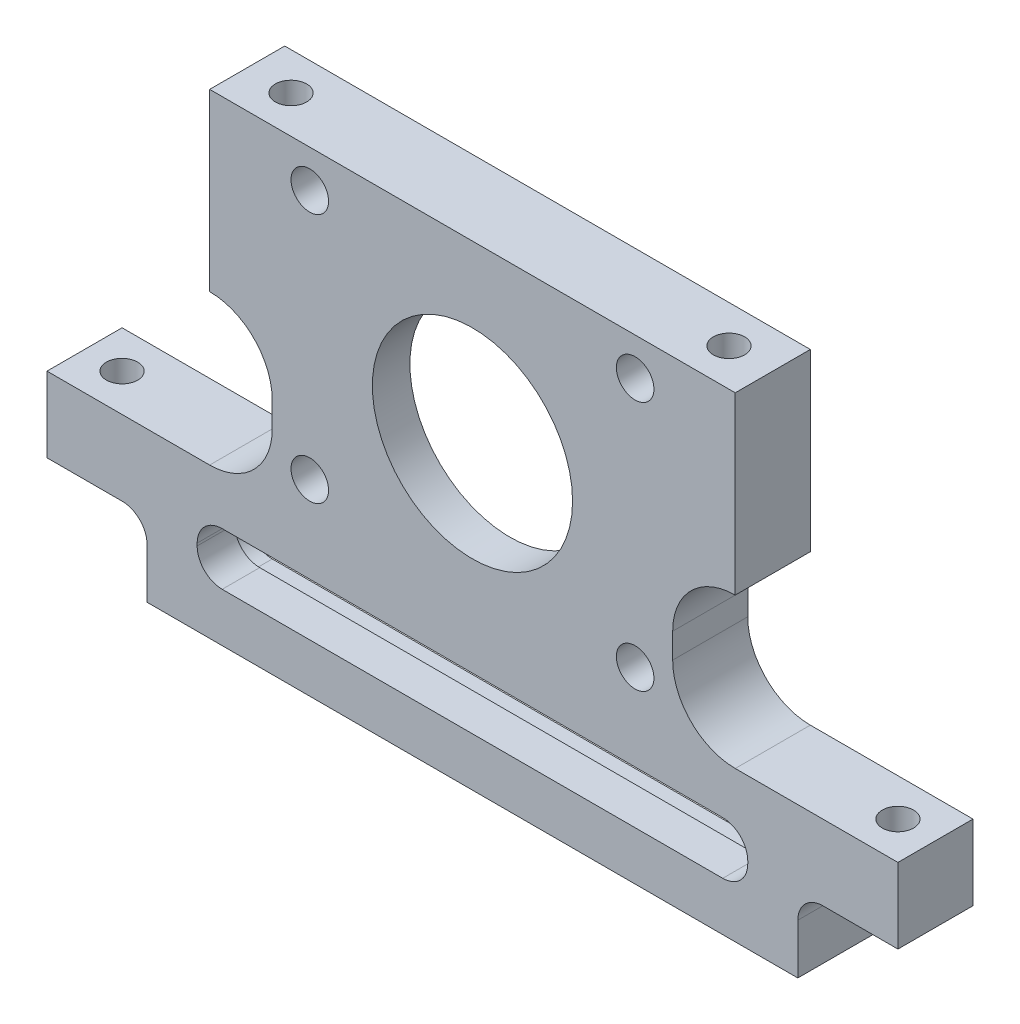
SolidWorks part; units mm, degrees
material "1060 Alloy"
ref_plane "Front Plane" through (0, 0, 0) normal (0, 0, 1) x (1, 0, 0)
ref_plane "Top Plane" through (0, 0, 0) normal (0, 1, 0) x (1, 0, 0)
ref_plane "Right Plane" through (0, 0, 0) normal (1, 0, 0) x (0, 0, -1)
sketch "Sketch1" plane through (0, 0, 0) normal (0, 0, 1) x (1, 0, 0)
  line L0 (18, 32) -> (50, 32)
  line L1 (8, 0) -> (8, -6)
  line L2 (50, 32) -> (50, 6)
  line L3 (18, 32) -> (18, 6)
  line L4 (12, 2.1) -> (56, 2.1)
  line L5 (12, 2.1) -> (12, -2.1)
  line L6 (12, -2.1) -> (56, -2.1)
  line L7 (56, 2.1) -> (56, -2.1)
  line L8 (8, -6) -> (60, -6)
  line L9 (60, -6) -> (60, 0)
  line L10 (8, 0) -> (0, 0)
  line L11 (0, 0) -> (0, 6)
  line L12 (0, 6) -> (18, 6)
  line L13 (50, 6) -> (68, 6)
  line L14 (68, 6) -> (68, 0)
  line L15 (68, 0) -> (60, 0)
  circle A0 centre (34, 18) radius 8
  dimension "D4" = 16
  dimension "D1" = 4.2
  dimension "D2" = 44
  dimension "D3" = 3.9
  dimension "D5" = 4
  dimension "D6" = 4
  dimension "D7" = 32
  dimension "D8" = 16
  dimension "D9" = 18
  dimension "D10" = 6
  dimension "D12" = 8
  dimension "D13" = 3.9
  dimension "D14" = 32
extrude "Boss-Extrude1" add sketch "Sketch1" along normal blind 6
sketch "Sketch3" plane through (0, 0, 0) normal (0, 0, -1) x (-1, 0, 0)
  circle A0 centre (-34, 18) radius 13
  dimension "D1" = 26
extrude "Cut-Extrude2" cut sketch "Sketch3" against normal offset from surface (3 mm away) 3 up to face at (34, 0, 6)
hole_wizard "Tap Drill for M3 Tap2" positions "Sketch5" profile "Sketch4" hole size "M3" standard "ISO"
sketch "Sketch5" plane through (38.1016, 0, -22.7468) normal (0, -1, 0) x (-1, 0, 0)
  line L3 (-29.8984, -28.7468) -> (-29.8984, -22.7468) construction
  line L4 (38.1016, -28.7468) -> (38.1016, -22.7468) construction
  line L5 (-21.8984, -28.7468) -> (-29.8984, -28.7468) construction
  point P0 (35.1016, -25.7468)
  point P2 (-26.8984, -25.7468)
  dimension "D1" = 3
  dimension "D2" = 3
  dimension "D3" = 3
sketch "Sketch4" plane through (3, 0, 3) normal (1, 0, 0) x (0, 0, -1)
  line L0 (0, 0) -> (0, 8.7511)
  line L1 (0, 8.7511) -> (1.25, 8)
  line L2 (1.25, 8) -> (1.25, 0)
  line L5 (1.25, 0) -> (0, 0)
  line L10 (0, 8.7511) -> (-1.25, 8) construction
  line L11 (0, -6.35) -> (0, 107.95) construction
  dimension "Hole Dia." = 2.5
  dimension "Hole Depth" = 8
  dimension "Drill Angle" = 118
sketch "Sketch10" plane through (0, 0, 0) normal (0, 0, -1) x (-1, 0, 0)
  line L0 (-56, -2.1) -> (-56, 2.1) construction
  line L1 (-58, 4) -> (-10, 4)
  line L2 (-58, 4) -> (-58, -4)
  line L3 (-58, -4) -> (-10, -4)
  line L4 (-10, 4) -> (-10, -4)
  line L8 (-56, 2.1) -> (-12, 2.1) construction
  line L9 (-12, 2.1) -> (-12, -2.1) construction
  dimension "D1" = 8
  dimension "D2" = 1.9
  dimension "D3" = 2
  dimension "D4" = 2
extrude "Cut-Extrude5" cut sketch "Sketch10" against normal blind 3
sketch "Sketch11" plane through (0, 0, 6) normal (0, 0, 1) x (1, 0, 0)
  line L1 (18, 32) -> (13, 32)
  line L2 (18, 32) -> (18, 18)
  line L3 (18, 18) -> (13, 18)
  line L4 (13, 32) -> (13, 18)
  line L6 (50, 32) -> (55, 32)
  line L7 (50, 32) -> (50, 18)
  line L8 (50, 18) -> (55, 18)
  line L9 (55, 32) -> (55, 18)
  line L10 (18, 6) -> (0, 6) construction
  dimension "D1" = 42
  dimension "D2" = 12
extrude "Boss-Extrude2" add sketch "Sketch11" against normal up to surface (6 mm away) up to face at (34, 0, 0)
fillet "Fillet1" radius 2 8 edges at (10, -4, 1.5) (12, -2.1, 4.5) (10, 4, 1.5) (12, 2.1, 4.5) (58, -4, 1.5) (58, 4, 1.5) (56, -2.1, 4.5) (56, 2.1, 4.5)
hole_wizard "M3x0.5 Tapped Hole1" positions "3DSketch1" profile "Sketch13" tap size "M3x0.5" standard "ANSI Metric"
sketch3d "3DSketch1"
  line L1 (13, 32, 0) -> (55, 32, 0) construction
  line L2 (13, 32, 0) -> (55, 32, 0) construction
  point P0 (51.5, 32, 3)
  point P2 (16.5, 32, 3)
  dimension "D1" = 35
  dimension "D2" = 3
  dimension "D3" = 3
  dimension "D4" = 1.5
sketch "Sketch13" plane through (51.5, 32, 3) normal (1, 0, 0) x (0, 0, 1)
  line L0 (0, 0) -> (0, 10.2511)
  line L1 (0, 10.2511) -> (1.25, 9.5)
  line L2 (1.25, 9.5) -> (1.25, 0)
  line L5 (1.25, 0) -> (0, 0)
  line L10 (0, 10.2511) -> (-1.25, 9.5) construction
  line L11 (0, -6.35) -> (0, 107.95) construction
  dimension "Tap Drill Dia." = 2.5
  dimension "Tap Drill Depth" = 9.5
  dimension "Drill Angle" = 118
cosmetic thread "Hole Thread1" parameters "D1"=8, "D2"=3
cosmetic thread "Hole Thread2" parameters "D1"=8, "D2"=3
fillet "Fillet3" radius 5 4 edges at (18, 18, 3) (18, 6, 3) (50, 6, 3) (50, 18, 3)
sketch "Sketch14" plane through (0, 0, 6) normal (0, 0, 1) x (1, 0, 0)
  line L0 (55, 32) -> (13, 32) construction
  line L1 (18, 32) -> (50, 32) construction
  line L2 (18, 32) -> (18, 6) construction
  line L3 (18, 6) -> (50, 6) construction
  line L4 (50, 32) -> (50, 6) construction
  line L5 (50, 11) -> (50, 13) construction
  line L6 (18, 13) -> (18, 11) construction
  line L7 (13, 6) -> (0, 6) construction
  circle A0 centre (21, 29) radius 1.5
  circle A1 centre (47, 29) radius 1.5
  circle A2 centre (21, 9) radius 1.5
  circle A3 centre (47, 9) radius 1.5
  dimension "D1" = 3
  dimension "D2" = 3
  dimension "D3" = 3
  dimension "D4" = 3
  dimension "D5" = 3
extrude "Cut-Extrude7" cut sketch "Sketch14" against normal through all
fillet "Fillet4" radius 2 2 edges at (8, 0, 3) (60, 0, 3)
